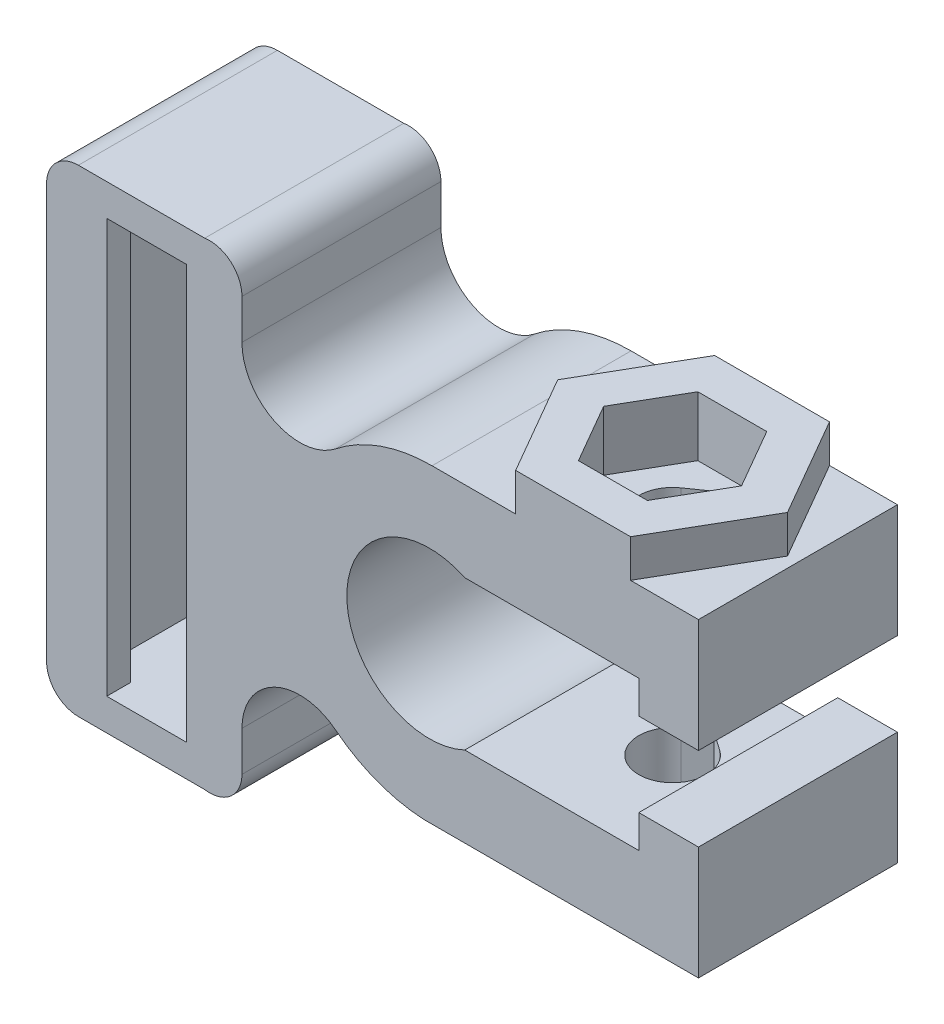
SolidWorks part; units mm, degrees
ref_plane "Front Plane" through (0, 0, 0) normal (0, 0, 1) x (1, 0, 0)
ref_plane "Top Plane" through (0, 0, 0) normal (0, 1, 0) x (1, 0, 0)
ref_plane "Right Plane" through (0, 0, 0) normal (1, 0, 0) x (0, 0, -1)
sketch "Sketch1" plane through (0, 0, 0) normal (0, 0, 1) x (1, 0, 0)
  line L0 (7.49, 0) -> (21.3, 0)
  line L1 (21.3, 0) -> (21.3, 4.05)
  line L2 (21.3, 4.05) -> (9.5556, 4.05)
  line L17 (9.5556, 11.55) -> (21.3, 11.55)
  line L18 (21.3, 11.55) -> (21.3, 15.6)
  line L19 (21.3, 15.6) -> (7.9113, 15.6)
  arc A1 (9.5556, 11.55) -> (9.5556, 4.05) centre (7.778, 7.8) ccw
  arc A2 (7.9113, 15.6) -> (7.49, 0) centre (7.9113, 7.7943) ccw
  dimension "D1" = 11.7444
extrude "Boss-Extrude1" add sketch "Sketch1" against normal blind 10
sketch "Sketch19" plane through (0, 0, 0) normal (0, -1, 0) x (1, 0, 0)
  line L0 (7.49, 0) -> (21.3, 0) construction
  line L1 (-22.3, -5) -> (22.1533, -5) construction
  line L2 (21.3, -10) -> (21.3, 0) construction
  line L6 (15, -5) -> (15, -8.8948) construction
  line L7 (15.9751, -6.3926) -> (15, -7.0753)
  line L8 (14.0249, -6.3926) -> (15, -7.0753)
  arc A2 (15.9751, -6.3926) -> (14.0249, -6.3926) centre (15, -5) ccw
  dimension "D1" = 6.3
  dimension "D3" = 5
  dimension "D7" = 3.4
  dimension "D9" = 35
extrude "Cut-Extrude6" cut sketch "Sketch19" against normal through all
sketch "Sketch21" plane through (0, 15.6, 0) normal (0, 1, 0) x (1, 0, 0)
  line L0 (21.3, 0) -> (7.9113, 0) construction
  line L1 (13.2679, 8) -> (11.5359, 5)
  line L2 (11.5359, 5) -> (13.2679, 2)
  line L3 (13.2679, 2) -> (16.7321, 2)
  line L4 (16.7321, 2) -> (18.4641, 5)
  line L5 (18.4641, 5) -> (16.7321, 8)
  line L6 (16.7321, 8) -> (13.2679, 8)
  line L8 (20.7735, 5) -> (17.8868, 10)
  line L9 (17.8868, 10) -> (12.1132, 10)
  line L10 (12.1132, 10) -> (9.2265, 5)
  line L11 (9.2265, 5) -> (12.1132, 0)
  line L12 (12.1132, 0) -> (17.8868, 0)
  line L13 (17.8868, 0) -> (20.7735, 5)
  circle A0 centre (15, 5) radius 3 construction
  dimension "D1" = 6
  dimension "D3" = 0
  dimension "D2" = 2
extrude "Boss-Extrude4" add sketch "Sketch21" along normal blind 1.9
sketch "Sketch22" plane through (0, 15.6, 0) normal (0, 1, 0) x (1, 0, 0)
  line L4 (16.7321, 8) -> (13.2679, 8)
  line L5 (16.7321, 8) -> (13.2679, 8)
  line L6 (13.2679, 8) -> (11.5359, 5)
  line L7 (13.2679, 8) -> (11.5359, 5)
  line L8 (11.5359, 5) -> (13.2679, 2)
  line L9 (11.5359, 5) -> (13.2679, 2)
  line L10 (13.2679, 2) -> (16.7321, 2)
  line L11 (13.2679, 2) -> (16.7321, 2)
  line L14 (16.7321, 2) -> (18.4641, 5)
  line L15 (16.7321, 2) -> (18.4641, 5)
  line L16 (18.4641, 5) -> (16.7321, 8)
  line L17 (18.4641, 5) -> (16.7321, 8)
  dimension "D1" = 0
extrude "Cut-Extrude7" cut sketch "Sketch22" against normal blind 1.1
sketch "Sketch31" plane through (0, 0, -10) normal (0, 0, -1) x (-1, 0, 0)
  line L0 (1.6426, 18.1943) -> (1.6426, 16.1943)
  line L3 (3.262, -2.6057) -> (9.862, -2.6057)
  line L4 (1.6426, -0.6057) -> (1.6426, -2.6087)
  line L5 (3.262, 18.1943) -> (9.862, 18.1943)
  line L6 (11.462, -2.6057) -> (11.462, 18.1943)
  line L7 (17.222, 13.6136) -> (17.222, -3.2714) construction
  line L8 (15.222, 13.6136) -> (17.222, 13.6136) construction
  line L9 (3.262, 11.7136) -> (10.2686, 11.7136) construction
  line L10 (3.262, -2.6057) -> (3.262, 18.1943)
  line L11 (17.222, -3.2714) -> (3.262, -3.2714) construction
  line L15 (3.512, -4.2057) -> (9.862, -4.2057)
  line L16 (3.512, 19.7943) -> (9.862, 19.7943)
  line L17 (9.862, -2.6057) -> (9.862, 18.1943)
  line L20 (3.262, 19.7943) -> (9.862, 19.7943) construction
  line L21 (3.262, -4.2057) -> (9.862, -4.2057) construction
  line L25 (11.462, 18.1943) -> (11.462, 19.7943) construction
  line L26 (9.862, 18.1943) -> (9.862, 19.7943) construction
  arc A0 (-7.49, 0) -> (-7.9113, 15.6) centre (-7.9113, 7.7943) ccw construction
  arc A1 (-3.0674, 1.6734) -> (-3.0674, 13.9152) centre (-7.9113, 7.7943) ccw
  arc A2 (1.6426, -2.6087) -> (3.512, -4.2057) centre (3.262, -2.6057) ccw
  arc A3 (3.512, 19.7943) -> (1.6426, 18.1943) centre (3.262, 18.1943) ccw
  arc A6 (-3.0674, 13.9152) -> (1.6426, 16.1943) centre (-1.2638, 16.1943) ccw
  arc A7 (11.462, 18.1943) -> (9.862, 19.7943) centre (9.862, 18.1943) ccw
  arc A8 (9.862, -4.2057) -> (11.462, -2.6057) centre (9.862, -2.6057) ccw
  arc A9 (-3.0674, 1.6734) -> (1.6426, -0.6057) centre (-1.2638, -0.6057) cw
  spline S0 degree 3 poles (10.2686, 11.7136) (10.7204, 11.7136) (11.1601, 11.7869) (11.8059, 11.9791) (12.0175, 12.0569) (12.429, 12.2323) (12.6299, 12.3304) (13.2219, 12.647) (13.6001, 12.8914) (14.1748, 13.243) (14.3688, 13.3585) (14.6749, 13.4981) (14.7791, 13.5385) (14.9957, 13.5966) (15.1087, 13.6136) (15.222, 13.6136) knots 0 0 0 0 0.25 0.25 0.375 0.375 0.5 0.5 0.75 0.75 0.875 0.875 0.9375 0.9375 1 1 1 1 construction
  dimension "D1" = 20.8
  dimension "D2" = 6.6
  dimension "D5" = 1.6
  dimension "D6" = 1.6
  dimension "D7" = 1.6
extrude "Boss-Extrude5" add sketch "Sketch31" against normal up to surface (10 mm away) up to face at (13.8494, 10.7338, 0)
sketch "Sketch32" plane through (0, 0, 0) normal (0, 0, 1) x (1, 0, 0)
  line L0 (-4.437, -2.6057) -> (-3.262, -2.6057)
  line L3 (-8.437, 18.1943) -> (-9.862, 18.1943)
  line L4 (-9.862, -2.6057) -> (-3.262, -2.6057)
  line L5 (-9.862, 18.1943) -> (-9.862, -2.6057)
  line L6 (-3.262, 18.1943) -> (-9.862, 18.1943)
  line L7 (-3.262, -2.6057) -> (-3.262, 18.1943)
  line L8 (-9.862, -2.6057) -> (-8.437, -2.6057)
  line L9 (-9.862, 18.1943) -> (-9.862, -2.6057)
  line L10 (-3.262, 18.1943) -> (-4.437, 18.1943)
  line L11 (-3.262, -2.6057) -> (-3.262, 18.1943)
  line L12 (-8.437, -2.6057) -> (-8.437, 18.1943)
  line L13 (-4.437, -2.6057) -> (-4.437, 18.1943)
  dimension "D1" = 0
extrude "Boss-Extrude6" add sketch "Sketch32" against normal blind 1.2
sketch "Sketch33" plane through (0, 11.55, 0) normal (0, -1, 0) x (1, 0, 0)
  line L0 (18.3, -10) -> (18.3, 0)
  line L4 (21.3, 0) -> (9.5556, 0)
  line L5 (9.5556, 0) -> (9.5556, -10)
  line L6 (9.5556, -10) -> (21.3, -10)
  line L7 (21.3, -10) -> (21.3, 0)
  line L8 (21.3, 0) -> (18.3, 0)
  line L10 (18.3, -10) -> (21.3, -10)
  line L11 (21.3, -10) -> (21.3, 0)
  dimension "D1" = 0
  dimension "D2" = 3
extrude "Boss-Extrude7" add sketch "Sketch33" along normal blind 1.65
sketch "Sketch34" plane through (0, 4.05, 0) normal (0, 1, 0) x (1, 0, 0)
  line L4 (21.3, 0) -> (21.3, 10)
  line L5 (18.3, 0) -> (21.3, 0)
  line L6 (18.3, 10) -> (18.3, 0)
  line L7 (21.3, 10) -> (18.3, 10)
  line L8 (21.3, 0) -> (21.3, 10)
  line L9 (18.3, 0) -> (21.3, 0)
  line L10 (18.3, 10) -> (18.3, 0)
  line L11 (21.3, 10) -> (18.3, 10)
  dimension "D1" = 0
extrude "Boss-Extrude8" add sketch "Sketch34" along normal blind 1.65
